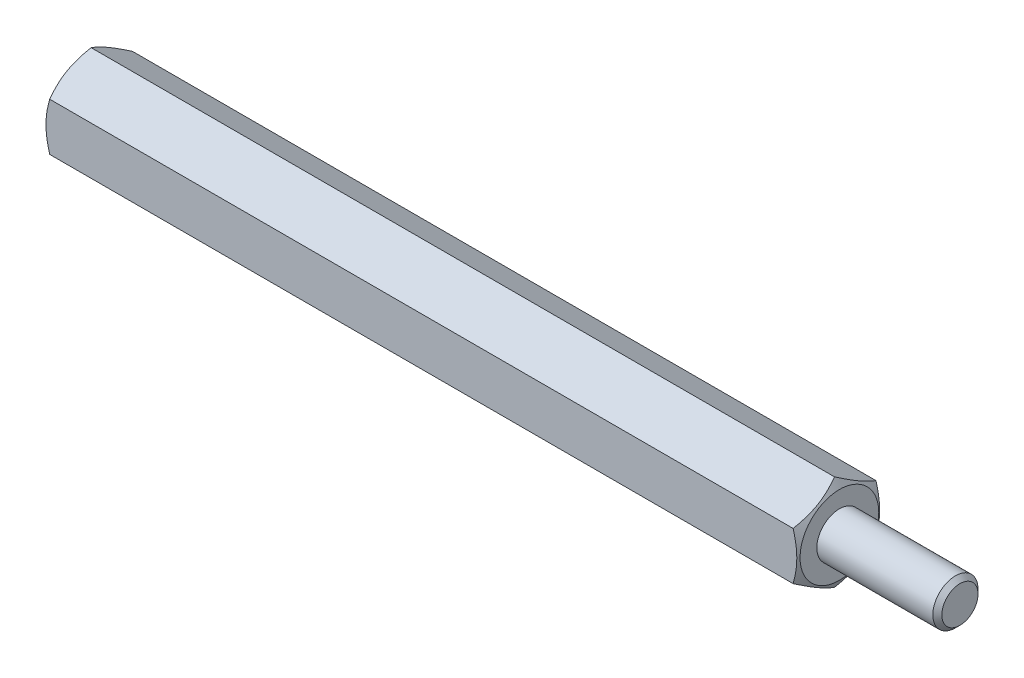
SolidWorks part; units mm, degrees
material "Brass"
ref_plane "Front Plane" through (0, 0, 0) normal (0, 0, 1) x (1, 0, 0)
ref_plane "Top Plane" through (0, 0, 0) normal (0, 1, 0) x (1, 0, 0)
ref_plane "Right Plane" through (0, 0, 0) normal (1, 0, 0) x (0, 0, -1)
sketch "Sketch1" plane through (0, 0, 0) normal (1, 0, 0) x (0, 0, -1)
  line L1 (0, 3.1754) -> (-2.75, 1.5877)
  line L2 (-2.75, 1.5877) -> (-2.75, -1.5877)
  line L3 (-2.75, -1.5877) -> (0, -3.1754)
  line L4 (0, -3.1754) -> (2.75, -1.5877)
  line L5 (2.75, -1.5877) -> (2.75, 1.5877)
  line L6 (2.75, 1.5877) -> (0, 3.1754)
  circle A0 centre (0, 0) radius 2.75 construction
extrude "Boss-Extrude1" add sketch "Sketch1" along normal blind 50
sketch "Sketch2" plane through (50, 0, 0) normal (1, 0, 0) x (0, 0, -1)
  circle A0 centre (0, 0) radius 1.5
extrude "Boss-Extrude2" add sketch "Sketch2" along normal blind 8
sketch "Sketch3" plane through (0, 0, 0) normal (-1, 0, 0) x (0, 0, 1)
  circle A0 centre (0, 0) radius 1.5
extrude "Cut-Extrude1" cut sketch "Sketch3" against normal blind 40
sketch "Sketch4" plane through (0, 0, 0) normal (0, 1, 0) x (1, 0, 0)
  line L0 (0, 0) -> (0, 2.6125)
  line L1 (0, 2.6125) -> (4.3921, 10.2198)
  line L2 (0, 2.6125) -> (0, 10.2198)
  line L3 (0, 10.2198) -> (4.3921, 10.2198)
  line L4 (0, 0) -> (-8.2035, 0) construction
  line L5 (50, 0) -> (50, 2.6125)
  line L6 (50, 2.6125) -> (45.6079, 10.2198)
  line L7 (50, 2.6125) -> (50, 10.2198)
  line L8 (50, 10.2198) -> (45.6079, 10.2198)
  line L9 (0, 0) -> (50, 0)
  point P11 (0, 0)
  point P12 (0, 0)
revolve "Cut-Revolve1" cut sketch "Sketch4" angle 360 about L4 region at (1.464, 0, -7.684) region at (48.536, 0, -7.684)
chamfer "Chamfer1" distance 0.3 angle 45 1 edges at (58, 0, -1.5)
